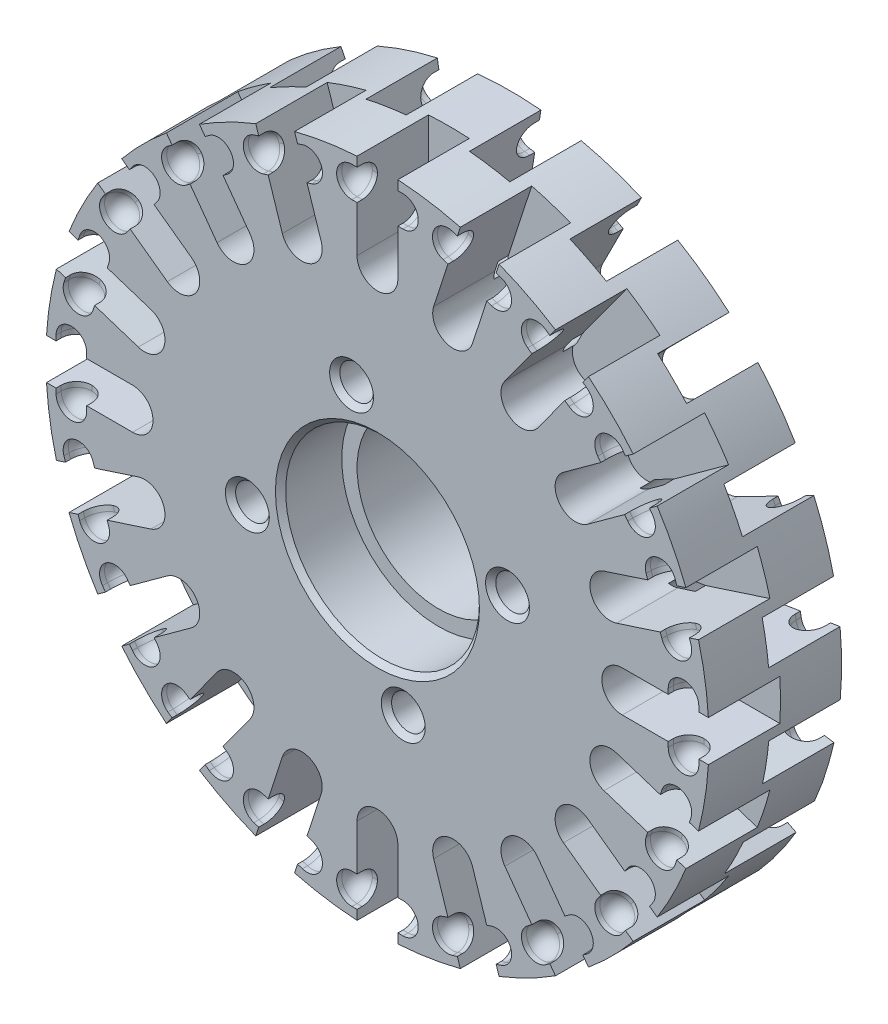
SolidWorks part; units mm, degrees
material "白色 POM"
ref_plane "前视基准面" through (0, 0, 0) normal (0, 0, 1) x (1, 0, 0)
ref_plane "上视基准面" through (0, 0, 0) normal (0, 1, 0) x (1, 0, 0)
ref_plane "右视基准面" through (0, 0, 0) normal (1, 0, 0) x (0, 0, -1)
sketch "草图1" plane through (0, 0, 0) normal (0, 0, 1) x (1, 0, 0)
  circle A0 centre (0, 0) radius 32.5
  dimension "D1" = 65
extrude "拉伸1" add sketch "草图1" along normal blind 13
sketch "草图10" plane through (0, 0, 13) normal (0, 0, 1) x (1, 0, 0)
  circle A0 centre (0, 0) radius 8
  dimension "D1" = 16
extrude "减速箱上的孔" cut sketch "草图10" against normal up to surface (13 mm away) up to face at (32.5, 0, 0)
sketch "草图6" plane through (0, 0, 0) normal (0, 0, -1) x (-1, 0, 0)
  circle A0 centre (0, 0) radius 30.7
  dimension "D1" = 61.4
extrude "和齿轮的连接" [suppressed] cut sketch "草图6" against normal blind 2
sketch "草图2" plane through (0, 0, 13) normal (0, 0, 1) x (1, 0, 0)
  circle A0 centre (0, 0) radius 9.5
  dimension "D1" = 19
extrude "轴承孔" cut sketch "草图2" against normal blind 6
sketch "草图3" plane through (0, 0, 13) normal (0, 0, 1) x (1, 0, 0)
  line L0 (0, 0) -> (0, 13) construction
  line L1 (0, 0) -> (-2.5362, 12.7502) construction
  circle A0 centre (0, 0) radius 13 construction
  circle A1 centre (-2.5362, 12.7502) radius 1.65
  dimension "D1" = 26
  dimension "D2" = 3.3
  dimension "D3" = 11.25
extrude "和车盖的孔" cut sketch "草图3" against normal blind 10
cosmetic thread "装饰螺纹线1" parameters "D2"=4
pattern_circular "阵列(圆周)1" count 4 over 360 about axis through (0, 0, 0) along (0, 0, 1) of "和车盖的孔"
cosmetic thread "装饰螺纹线2" parameters "D2"=4
cosmetic thread "装饰螺纹线3" parameters "D2"=4
cosmetic thread "装饰螺纹线4" parameters "D2"=4
sketch "草图4" plane through (0, 0, 13) normal (0, 0, 1) x (1, 0, 0)
  circle A0 centre (0, 0) radius 20 construction
  circle A1 centre (0, 20) radius 0.625
  dimension "D1" = 40
  dimension "D2" = 1.25
extrude "拉伸4" [suppressed] cut sketch "草图4" against normal blind 10
cosmetic thread "装饰螺纹线5" [suppressed] parameters "D2"=1.6
pattern_circular "阵列(圆周)2" [suppressed] count 6 every 60
sketch "草图5" plane through (0, 0, 13) normal (0, 0, 1) x (1, 0, 0)
  line L0 (-24, 2) -> (-32.4384, 2)
  line L1 (-24, -2) -> (-32.4384, -2)
  circle A0 centre (0, 0) radius 24 construction
  arc A1 (-24, -2) -> (-24, 2) centre (-24, 0) ccw
  arc A2 (-32.4384, 2) -> (-32.4384, -2) centre (0, 0) ccw
  circle A3 centre (0, 0) radius 32.5 construction
  dimension "D1" = 48
  dimension "D2" = 4
extrude "给小轮子留的槽1" cut sketch "草图5" against normal blind 7
pattern_circular "阵列(圆周)3" count 20 over 360 about axis through (0, 0, 0) along (0, 0, 1) of "给小轮子留的槽1"
sketch "草图8" plane through (0, 0, 13) normal (0, 0, 1) x (1, 0, 0)
  circle A0 centre (0, 0) radius 23
  dimension "D1" = 46
sketch "草图9" [suppressed] plane through (0, 0, 0) normal (1, 0, 0) x (0, 0, -1)
  line L0 (-8.5, -24) -> (-9.5, -24)
  line L1 (-9.5, -24) -> (-9.5, -22)
  line L2 (-8.5, -22) -> (-9.5, -22)
  line L3 (-9.5, 9.5) -> (-9.5, -9.5) construction
  line L4 (0, 0) -> (-9.5, 0) construction
  line L5 (-9.5, 9.1187) -> (-9.5, 5.271) construction
  arc A0 (-8.5, -24) -> (-8.5, -22) centre (-8.5, -23) ccw
  dimension "D1" = 1
  dimension "D4" = 23
  dimension "D2" = 1
  dimension "D3" = 1
sweep "切除-扫描1" [suppressed] cut profiles "草图9" path "草图8"
chamfer "倒角1" distance 0.5 angle 45 5 edges at (12.7502, 0.8862, 13) (0.8862, -12.7502, 13) (-12.7502, -0.8862, 13) (-0.8862, 12.7502, 13) (9.5, 0, 13)
chamfer "倒角2" [suppressed] distance 0.25 angle 45
sketch "草图11" plane through (0, 0, 13) normal (0, 0, 1) x (1, 0, 0)
  line L0 (-22.5, 3.75) -> (-22.5, -3.75) construction
  line L1 (-23.5, 3.75) -> (-21.5, 3.75) construction
  line L2 (-23.5, 3.75) -> (-23.5, -3.75)
  line L3 (-23.5, -3.75) -> (-21.5, -3.75)
  line L4 (-21.5, 3.75) -> (-21.5, -3.75)
  line L5 (-22.5, 0) -> (0, 0) construction
  line L6 (-20.8002, 11.5613) -> (-23.3654, 4.5136)
  line L7 (-23.3654, 4.5136) -> (-21.486, 3.8296) construction
  line L8 (-21.486, 3.8296) -> (-18.9208, 10.8773)
  line L9 (-18.9208, 10.8773) -> (-20.8002, 11.5613)
  line L10 (-19.8605, 11.2193) -> (-22.4257, 4.1716) construction
  line L11 (0, 0) -> (-21.1431, 7.6955) construction
  arc A0 (-21.486, 3.8296) -> (-21.5, 3.75) centre (0, 0) ccw
  arc A1 (-23.3654, 4.5136) -> (-23.5, 3.75) centre (0, 0) ccw
  arc A2 (-20.6848, 25.0676) -> (-25.0676, 20.6848) centre (0, 0) ccw construction
  arc A3 (-22.4257, 4.1716) -> (-22.5, 3.75) centre (0, 0) ccw construction
  dimension "D1" = 7.5
  dimension "D2" = 2
  dimension "D3" = 22.5
  dimension "D4" = 20
sketch "草图12" [suppressed] plane through (0, 0, 9.5) normal (0, 0, 1) x (1, 0, 0)
  line L1 (-20.3304, 11.3903) -> (-22.8955, 4.3426) construction
  line L3 (-22.3654, 5.7991) -> (-22.8955, 4.3426)
  line L5 (-23, 3.75) -> (-23, -3.75) construction
  line L7 (-23, 3.75) -> (-23, 0)
  line L9 (-24.1536, 6.45) -> (-18.6066, 4.4311) construction
  line L11 (-24.1536, 6.45) -> (-18.6066, 4.4311) construction
  line L13 (0, 0) -> (-24.5802, 0) construction
  arc A1 (-22.8955, 4.3426) -> (-23, 3.75) centre (0, 0) ccw construction
  arc A3 (-22.8955, 4.3426) -> (-23, 3.75) centre (0, 0) ccw
sketch "草图13" [suppressed] plane through (0, 0, 0) normal (0, 1, 0) x (1, 0, 0)
  line L0 (0, -9.5) -> (-24.5802, -9.5) construction
  line L1 (-24, -9.5) -> (-22, -9.5)
  line L2 (-24, -9.5) -> (-24, -7.5)
  line L3 (-24, -7.5) -> (-22, -7.5)
  line L4 (-22, -9.5) -> (-22, -7.5)
  line L5 (-23, -7.5) -> (-23, -9.5) construction
  dimension "D1" = 2
  dimension "D2" = 2
sweep "切除-扫描2" [suppressed] cut profiles "草图13" path "草图12"
sketch "草图15" plane through (0, 0, 13) normal (0, 0, 1) x (1, 0, 0)
  line L0 (-30, 4) -> (-30, -4) construction
  line L2 (-31.5, 2.5) -> (-31.5, -2.5)
  line L4 (-28.5, 2.5) -> (-28.5, -2.5)
  line L5 (-30, 0) -> (0, 0) construction
  arc A0 (-31.5, -2.5) -> (-28.5, -2.5) centre (-30, -2.5) ccw
  arc A1 (-28.5, 2.5) -> (-31.5, 2.5) centre (-30, 2.5) ccw
  dimension "D1" = 30
  dimension "D2" = 3
  dimension "D3" = 8
extrude "小棍子孔1" cut sketch "草图15" against normal blind 2
fillet "圆角2" [suppressed] radius 1
fillet "圆角3" radius 1.5 6 edges at (-28.5, -2.25, 11) (-28.5, 2.25, 11) (-31.5, -2.25, 11) (-31.5, 2.25, 11) (-30, -4, 11) (-30, 4, 11)
pattern_circular "阵列(圆周)6" count 20 over 360 about axis through (0, 0, 0) along (0, 0, 1) of "小棍子孔1", "圆角3"
sketch "草图17" [suppressed] plane through (0, 0, 2) normal (0, 0, -1) x (-1, 0, 0)
  line L0 (0, 0) -> (-11.667, 17.4609) construction
  line L1 (0, 0) -> (2.5362, 12.7502) construction
  circle A0 centre (0, 0) radius 21 construction
  dimension "D1" = 42
  dimension "D2" = 45
sketch "草图19" [suppressed] plane through (0, 0, 2) normal (0, 0, -1) x (-1, 0, 0)
  line L0 (0, 0) -> (-21.7082, 21.7082) construction
  circle A0 centre (0, 0) radius 23.9 construction
  circle A1 centre (-16.8999, 16.8999) radius 0.75
  arc A2 (-19.6247, 23.6085) -> (-23.6085, 19.6247) centre (0, 0) ccw construction
  dimension "D1" = 47.8
  dimension "D2" = 1.5
extrude "切除-拉伸1" [suppressed] cut sketch "草图19" against normal blind 6
cosmetic thread "装饰螺纹线6" parameters "D2"=2
pattern_circular "阵列(圆周)7" [suppressed] count 4 every 90
sketch "草图22" plane through (0, 0, 0) normal (0, 0, -1) x (-1, 0, 0)
  line L0 (20.5067, 12.6283) -> (28.0346, 16.4411)
  line L1 (22.3141, 9.0599) -> (29.842, 12.8727)
  line L3 (28.9933, 14.6847) -> (0, 0) construction
  circle A0 centre (0, 0) radius 24 construction
  circle A1 centre (0, 0) radius 32.5 construction
  arc A3 (20.5067, 12.6283) -> (22.3141, 9.0599) centre (21.4104, 10.8441) ccw
  dimension "D1" = 48
  dimension "D2" = 4
extrude "切除-拉伸2" cut sketch "草图22" against normal blind 7 and the other way through all
pattern_circular "阵列(圆周)8" count 20 over 360 about axis through (0, 0, 0) along (0, 0, 1) of "切除-拉伸2"
sketch "草图23" plane through (0, 0, 0) normal (0, 0, -1) x (-1, 0, 0)
  line L0 (0, 0) -> (32.1121, 5.0066) construction
  line L1 (30.027, 2.1513) -> (29.2568, 7.0916) construction
  line L2 (28.5449, 1.9202) -> (27.7747, 6.8605)
  line L3 (31.5091, 2.3824) -> (30.7389, 7.3227)
  arc A0 (32.3593, 3.0209) -> (31.7431, 6.9732) centre (0, 0) ccw construction
  arc A1 (28.5449, 1.9202) -> (31.5091, 2.3824) centre (30.027, 2.1513) ccw
  arc A2 (30.7389, 7.3227) -> (27.7747, 6.8605) centre (29.2568, 7.0916) ccw
  point P8 (29.6419, 4.6214)
  point P13 (0, 0)
  point P14 (0, 0)
  dimension "D1" = 1.5
  dimension "D2" = 5
  dimension "D3" = 30
extrude "小棍子孔2" cut sketch "草图23" against normal blind 2
fillet "圆角4" radius 1.5 6 edges at (-28.5064, 2.1672, 2) (-31.4706, 2.6294, 2) (-30.2581, 0.6692, 2) (-27.8132, 6.6135, 2) (-30.7774, 7.0757, 2) (-29.0257, 8.5737, 2)
pattern_circular "阵列(圆周)11" count 20 over 360 about axis through (0, 0, 0) along (0, 0, 1) of "小棍子孔2", "圆角4"
